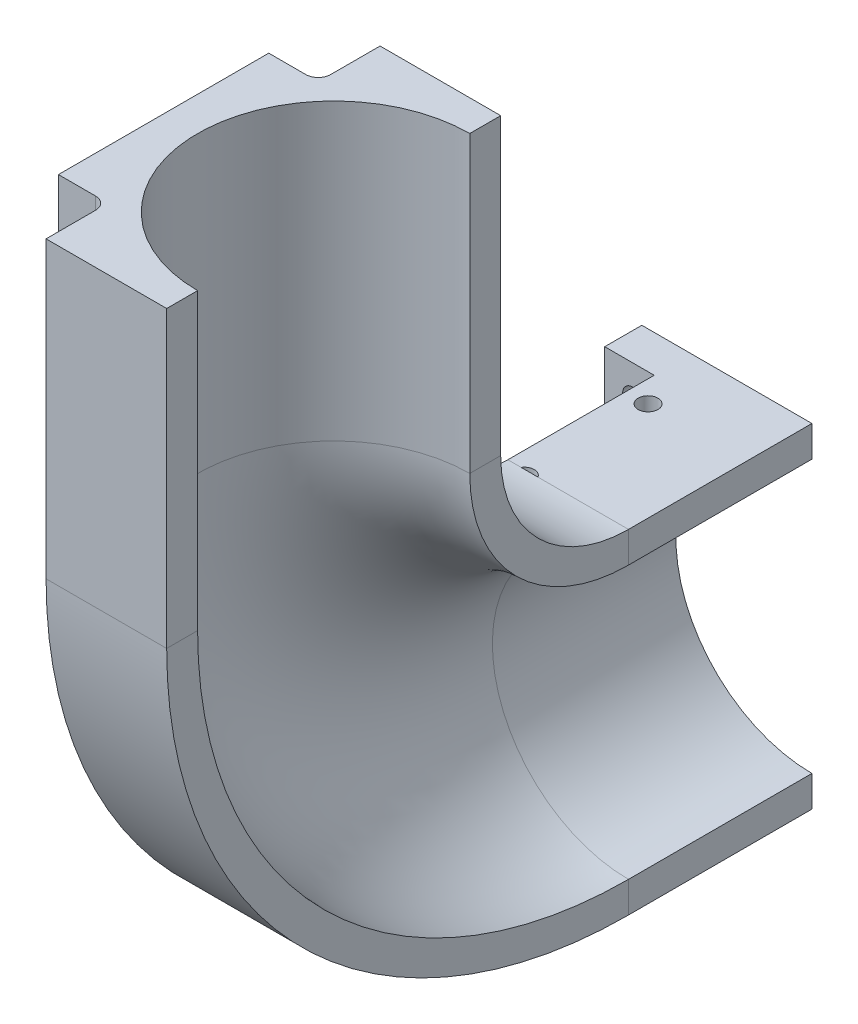
SolidWorks part; units mm, degrees
ref_plane "Front" through (0, 0, 0) normal (0, 0, 1) x (1, 0, 0)
ref_plane "Top" through (0, 0, 0) normal (0, 1, 0) x (1, 0, 0)
ref_plane "Right" through (0, 0, 0) normal (1, 0, 0) x (0, 0, -1)
sketch "草图1" plane through (0, 0, 0) normal (0, 0, 1) x (1, 0, 0)
  line L0 (0, 0) -> (27.5, 0)
  line L1 (0, 0) -> (0, -54)
  line L2 (0, -54) -> (27.5, -54)
  line L3 (27.5, -54) -> (27.5, -49)
  line L4 (27.5, 0) -> (27.5, -5)
  arc A0 (27.5, -5) -> (27.5, -49) centre (27.5, -27) ccw
  point P14 (0, -27)
  dimension "D3" = 44
  dimension "D1" = 54
  dimension "D2" = 27.5
extrude "凸台-拉伸1" add sketch "草图1" along normal blind 6
sketch "草图2" plane through (0, 0, 6) normal (0, 0, 1) x (1, 0, 0)
  line L0 (8, 0) -> (8, -8)
  line L1 (6, -10) -> (0, -10)
  line L2 (8, -46) -> (8, -54)
  line L3 (6, -44) -> (0, -44)
  line L5 (0, 0) -> (0, -54)
  line L6 (0, -54) -> (27.5, -54)
  line L7 (27.5, -54) -> (27.5, -49)
  line L8 (27.5, -5) -> (27.5, 0)
  line L9 (27.5, 0) -> (0, 0)
  line L10 (0, -10) -> (0, -44)
  line L11 (8, -54) -> (27.5, -54)
  line L12 (27.5, -54) -> (27.5, -49)
  line L13 (27.5, -5) -> (27.5, 0)
  line L14 (27.5, 0) -> (8, 0)
  arc A0 (8, -46) -> (6, -44) centre (6, -46) ccw
  arc A1 (27.5, -5) -> (27.5, -49) centre (27.5, -27) ccw
  arc A2 (27.5, -5) -> (27.5, -49) centre (27.5, -27) ccw
  arc A3 (8, -8) -> (6, -10) centre (6, -8) cw
  point P17 (8, -10)
  dimension "D4" = 2
  dimension "D2" = 10
  dimension "D3" = 8
  dimension "D1" = 0
sketch "草图3" plane through (27.5, 0, 0) normal (1, 0, 0) x (0, 0, -1)
  line L0 (-6, -27) -> (-29.66, -27)
  line L1 (-6, -10) -> (-6, -44) construction
  line L2 (-77.32, 20.66) -> (-77.32, 68.26)
  arc A0 (-29.66, -27) -> (-77.32, 20.66) centre (-29.66, 20.66) cw
  dimension "D2" = 47.66
  dimension "D1" = 23.66
  dimension "D3" = 47.6
sweep "扫描1" add profiles "草图2" path "草图3"
sketch "草图4" plane through (0, 0, 6) normal (0, 0, 1) x (1, 0, 0)
  line L0 (0, 0) -> (0, -10) construction
  line L1 (8, 0) -> (0, 0) construction
  circle A0 centre (4.5, -5) radius 1.6
  dimension "D1" = 3.2
  dimension "D2" = 4.5
  dimension "D3" = 5
extrude "切除-拉伸1" cut sketch "草图4" against normal through all contours A0
ref_plane "基准面2" through (0, -27, 0) normal (0, 1, 0) x (1, 0, 0)
mirror "镜向1" about plane through (0, -27, 0) normal (0, 1, 0) of "切除-拉伸1"
sketch "草图5" plane through (0, 0, 0) normal (0, 1, 0) x (1, 0, 0)
  circle A0 centre (11.5, -10.5) radius 1.6 construction
  circle A1 centre (11.5, -30.5) radius 1.6 construction
  circle A2 centre (11.5, -10.5) radius 1.6
  circle A3 centre (11.5, -30.5) radius 1.6
extrude "切除-拉伸2" cut sketch "草图5" against normal blind 20
